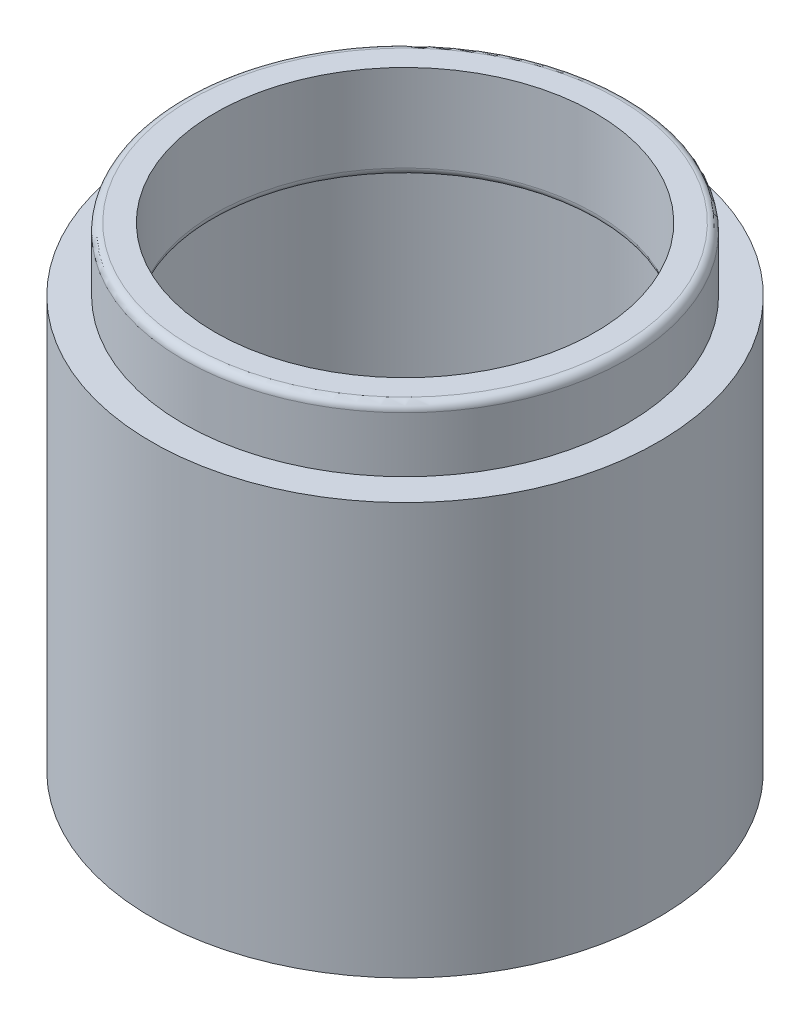
SolidWorks part; units mm, degrees
material "PLA Yellow"
ref_plane "Front Plane" through (0, 0, 0) normal (0, 0, 1) x (1, 0, 0)
ref_plane "Top Plane" through (0, 0, 0) normal (0, 1, 0) x (1, 0, 0)
ref_plane "Right Plane" through (0, 0, 0) normal (1, 0, 0) x (0, 0, -1)
sketch "Sketch1" plane through (0, 0, 0) normal (1, 0, 0) x (0, 0, -1)
  line L0 (0, -32.3252) -> (0, 32.3252) construction
  line L1 (22.225, 23.8125) -> (22.225, 17.4625)
  line L2 (22.225, 17.4625) -> (25.4, 17.4625)
  line L3 (25.4, 17.4625) -> (25.4, -23.8125)
  line L4 (25.4, -23.8125) -> (22.225, -23.8125)
  line L5 (22.225, -23.8125) -> (22.225, -17.4625)
  line L6 (22.225, -17.4625) -> (9.525, -17.4625)
  line L8 (19.05, 23.8125) -> (22.225, 23.8125)
  line L9 (9.525, -17.4625) -> (9.525, -14.2875)
  line L10 (9.525, -14.2875) -> (22.4, -14.2875)
  line L11 (22.4, -14.2875) -> (22.4, 14.2875)
  line L12 (22.4, 14.2875) -> (19.05, 14.2875)
  line L13 (19.05, 14.2875) -> (19.05, 23.8125)
  point P4 (0, 0)
  point P18 (22.4, 0)
  point P19 (15.9625, -14.2875)
  dimension "D1" = 12.7
  dimension "D2" = 3.175
  dimension "D3" = 6.35
  dimension "D4" = 50.8
  dimension "D5" = 31.75
  dimension "D6" = 3.175
  dimension "D7" = 3
  dimension "D8" = 3.175
  dimension "D9" = 3.175
revolve "Revolve1" add sketch "Sketch1" angle 360 about L0
fillet "Fillet1" radius 0.7937 6 edges at (0, -14.2875, -9.525) (0, -17.4625, -9.525) (0, -17.4625, -22.225) (0, -23.8125, -22.225) (0, 23.8125, -22.225) (0, 14.2875, -19.05)
sketch "Sketch2" plane through (0, -14.2875, 0) normal (0, 1, 0) x (1, 0, 0)
  line L1 (-3.175, 0) -> (3.175, 0)
  line L2 (-3.175, 0) -> (-3.175, 25.2008)
  line L3 (-3.175, 25.2008) -> (3.175, 25.2008)
  line L4 (3.175, 0) -> (3.175, 25.2008)
  line L5 (-3.175, 0) -> (3.175, 25.2008) construction
  line L6 (-3.175, 25.2008) -> (3.175, 0) construction
  circle A0 centre (0, 0) radius 25.4 construction
  point P4 (0, 12.6004)
  dimension "D2" = 6.35
extrude "Boss-Extrude1" add sketch "Sketch2" against normal up to surface (3.175 mm away) up to face at (0, -17.4625, -10.3188)
fillet "Fillet2" radius 1.5875 2 edges at (3.175, -15.875, 0) (-3.175, -15.875, 0)
